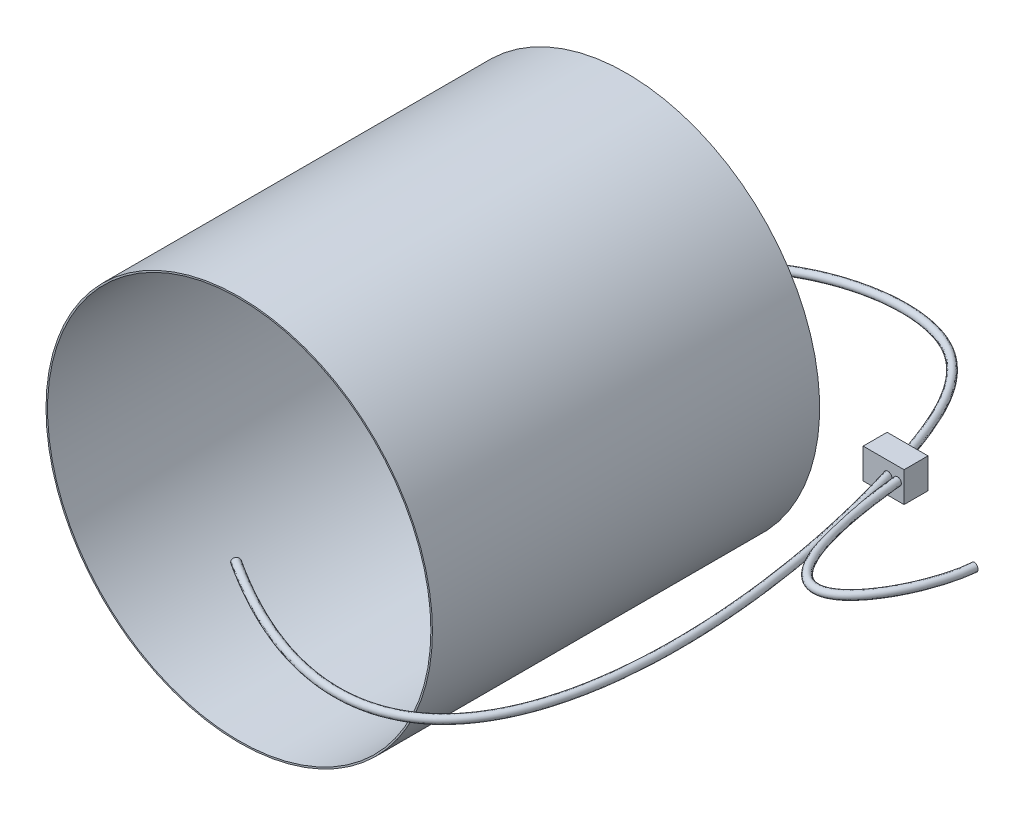
SolidWorks part; units mm, degrees
ref_plane "Front Plane" through (0, 0, 0) normal (0, 0, 1) x (1, 0, 0)
ref_plane "Top Plane" through (0, 0, 0) normal (0, 1, 0) x (1, 0, 0)
ref_plane "Right Plane" through (0, 0, 0) normal (1, 0, 0) x (0, 0, -1)
sketch "Sketch1" plane through (0, 0, 0) normal (0, 0, 1) x (1, 0, 0)
  circle A0 centre (0, 0) radius 250
  circle A1 centre (0, 0) radius 248
  dimension "D1" = 500
  dimension "D2" = 2
extrude "Boss-Extrude1" add sketch "Sketch1" along normal blind 500
sketch "Sketch2" plane through (0, 0, 0) normal (0, 0, -1) x (-1, 0, 0)
  circle A0 centre (0, 0) radius 250
extrude "Boss-Extrude2" add sketch "Sketch2" along normal blind 1
sketch "Sketch3" plane through (0, 0, -1) normal (0, 0, -1) x (-1, 0, 0)
  circle A0 centre (0, 0) radius 5
  dimension "D1" = 10
sketch "Sketch5" plane through (0, 0, 0) normal (0, 1, 0) x (1, 0, 0)
  line L1 (250, 1) -> (-250, 1) construction
  spline S0 degree 3 poles (0, 1) (-12.3928, 126.3123) (261.9886, 239.6414) (470.6696, -232.3135) (472.1883, -825.9929) (45.2081, -549.2993) knots 0 0 0 0 0.237045 0.3654 1 1 1 1
sweep "Sweep2" add profiles "Sketch3" path "Sketch5"
sketch "Sketch6" plane through (0, 0, 0) normal (0, 0, 1) x (1, 0, 0)
  line L1 (338.3026, 17.1513) -> (391.2184, 17.1513)
  line L2 (338.3026, 17.1513) -> (338.3026, -21.998)
  line L3 (338.3026, -21.998) -> (391.2184, -21.998)
  line L4 (391.2184, 17.1513) -> (391.2184, -21.998)
  line L5 (338.3026, 17.1513) -> (391.2184, -21.998) construction
  line L6 (338.3026, -21.998) -> (391.2184, 17.1513) construction
  point P4 (364.7605, -2.4234)
extrude "Boss-Extrude3" add sketch "Sketch6" along normal blind 31 separate body
sketch "Sketch7" plane through (0, 0, 31) normal (0, 0, 1) x (1, 0, 0)
  circle A0 centre (382.7087, 0) radius 5
  point P2 (382.7087, 0)
sketch "Sketch8" plane through (0, 0, 0) normal (0, 1, 0) x (1, 0, 0)
  line L0 (377.7087, -31) -> (387.7087, -31) construction
  spline S0 degree 3 poles (382.7087, -31) (414.3312, -339.5763) (522.7312, -157.9203) (528.967, -77.0978) knots 0 0 0 0 1 1 1 1
  point P2 (480.3166, -143.8852)
  point P4 (487.1892, -184.7838)
  point P6 (528.967, -77.0978)
sweep "Sweep3" add profiles "Sketch7" path "Sketch8"
